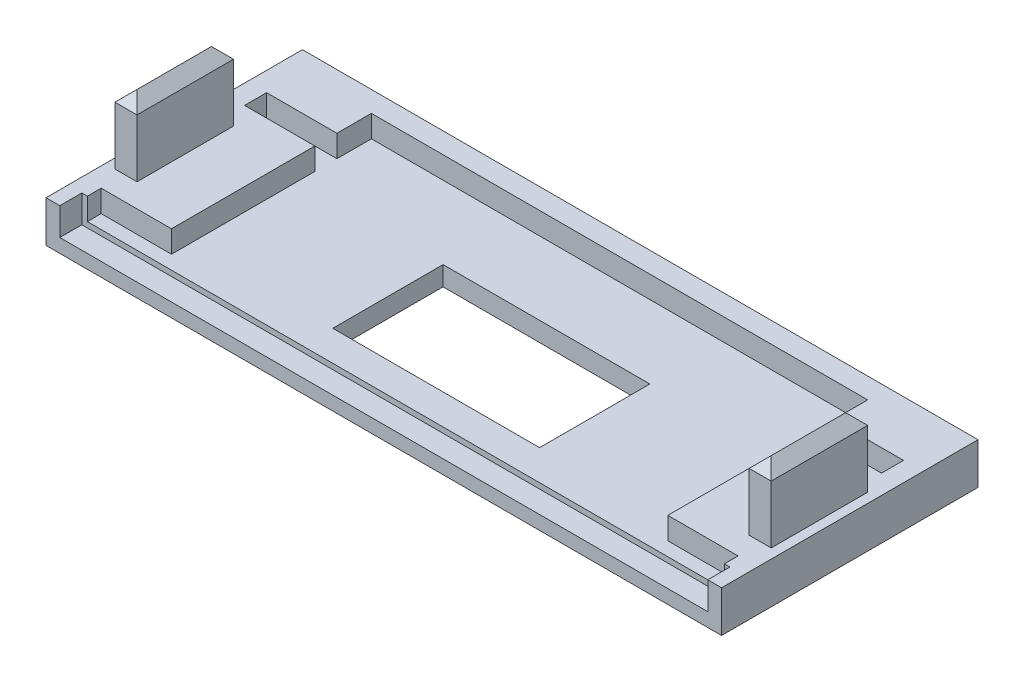
SolidWorks part; units mm, degrees
ref_plane "Plan de face" through (0, 0, 0) normal (0, 0, 1) x (1, 0, 0)
ref_plane "Plan de dessus" through (0, 0, 0) normal (0, 1, 0) x (1, 0, 0)
ref_plane "Plan de droite" through (0, 0, 0) normal (1, 0, 0) x (0, 0, -1)
sketch "Esquisse1" plane through (0, 0, 0) normal (0, 0, 1) x (1, 0, 0)
  line L1 (24.5, -1.5) -> (-24.5, -1.5)
  line L2 (24.5, -1.5) -> (24.5, 1.5)
  line L3 (24.5, 1.5) -> (-24.5, 1.5)
  line L4 (-24.5, -1.5) -> (-24.5, 1.5)
  line L5 (24.5, -1.5) -> (-24.5, 1.5) construction
  line L6 (24.5, 1.5) -> (-24.5, -1.5) construction
  point P1 (0, 0)
  dimension "D1" = 3
  dimension "D2" = 49
extrude "Boss.-Extru.1" add sketch "Esquisse1" along normal blind 18.6
sketch "Esquisse5" plane through (0, 1.5, 0) normal (0, 1, 0) x (1, 0, 0)
  line L2 (-23.1, -4) -> (-23.1, -5.6)
  line L4 (23.1, -4) -> (23.1, -5.6)
  line L6 (-23.1, -16) -> (-23.1, -17.6)
  line L7 (-23.1, -17.6) -> (23.1, -17.6)
  line L8 (23.1, -16) -> (23.1, -17.6)
  line L9 (-23.1, -4) -> (-18, -4)
  line L10 (-18, -4) -> (-18, -1.5)
  line L11 (-18, -5.6) -> (-18, -16)
  line L16 (18, -5.6) -> (18, -16)
  line L17 (-18, -5.6) -> (-23.1, -5.6)
  line L18 (18, -5.6) -> (23.1, -5.6)
  line L19 (23.1, -16) -> (18, -16)
  line L20 (-23.1, -16) -> (-18, -16)
  line L21 (-18, -1.5) -> (18, -1.5)
  line L22 (18, -1.5) -> (18, -4)
  line L23 (18, -4) -> (23.1, -4)
  line L24 (24.5, 0) -> (-24.5, 0) construction
  point P13 (0, -17.6)
  point P19 (0, 0)
  point P20 (0, 0)
  dimension "D1" = 1.6
  dimension "D2" = 1.6
  dimension "D3" = 4
  dimension "D4" = 1.6
  dimension "D5" = 46.2
  dimension "D6" = 46.2
  dimension "D7" = 4
  dimension "D8" = 1.5
  dimension "D9" = 18
  dimension "D10" = 18
  dimension "D11" = 1.6
  dimension "D12" = 10.4
extrude "Enlèv. mat.-Extru.2" cut sketch "Esquisse5" against normal blind 1.6
sketch "Esquisse6" plane through (0, -0.1, 0) normal (0, 1, 0) x (1, 0, 0)
  line L0 (-23.1, -5.6) -> (-18, -5.6) construction
  line L1 (7.5, -14.8) -> (-7.5, -14.8)
  line L2 (7.5, -14.8) -> (7.5, -6.8)
  line L3 (7.5, -6.8) -> (-7.5, -6.8)
  line L4 (-7.5, -14.8) -> (-7.5, -6.8)
  line L5 (7.5, -14.8) -> (-7.5, -6.8) construction
  line L6 (7.5, -6.8) -> (-7.5, -14.8) construction
  point P0 (0, -10.8)
  dimension "D1" = 15
  dimension "D2" = 8
  dimension "D3" = 5.2
extrude "Enlèv. mat.-Extru.3" cut sketch "Esquisse6" against normal up to next
sketch "Esquisse7" plane through (0, 1.5, 0) normal (0, 1, 0) x (1, 0, 0)
  line L0 (-24.5, -18.6) -> (-24.5, 0) construction
  line L1 (-23.8, -7.3) -> (-22.2, -7.3)
  line L2 (-23.8, -7.3) -> (-23.8, -14.3)
  line L3 (-23.8, -14.3) -> (-22.2, -14.3)
  line L4 (-22.2, -7.3) -> (-22.2, -14.3)
  line L5 (-23.8, -7.3) -> (-22.2, -14.3) construction
  line L6 (-23.8, -14.3) -> (-22.2, -7.3) construction
  line L9 (-18, -16) -> (-23.1, -16) construction
  point P0 (-23, -10.8)
  dimension "D1" = 1.6
  dimension "D2" = 7
  dimension "D3" = 5.2
  dimension "D4" = 1.5
extrude "Boss.-Extru.2" add sketch "Esquisse7" along normal blind 5
chamfer "Chanfrein1" distance 0.8 angle 45 4 edges at (-23, 6.5, 14.3) (-23.8, 6.5, 10.8) (-23, 6.5, 7.3) (-22.2, 6.5, 10.8)
mirror "Symétrie1" about plane through (0, 0, 0) normal (1, 0, 0) of "Chanfrein1", "Boss.-Extru.2"
sketch "Esquisse8" plane through (0, 0, 18.6) normal (0, 0, 1) x (1, 0, 0)
  line L0 (-23.5, 1.5) -> (-23.5, -0.5)
  line L1 (24.5, 1.5) -> (-24.5, 1.5) construction
  line L2 (-23.5, -0.5) -> (23.5, -0.5)
  line L3 (23.5, -0.5) -> (23.5, 1.5)
  line L4 (23.5, 1.5) -> (-23.5, 1.5)
  line L5 (-24.5, 1.5) -> (-24.5, -1.5) construction
  line L6 (-24.5, -1.5) -> (24.5, -1.5) construction
  line L7 (24.5, -1.5) -> (24.5, 1.5) construction
  dimension "D1" = 1
  dimension "D2" = 1
  dimension "D3" = 1
extrude "Enlèv. mat.-Extru.4" cut sketch "Esquisse8" against normal blind 1.6
